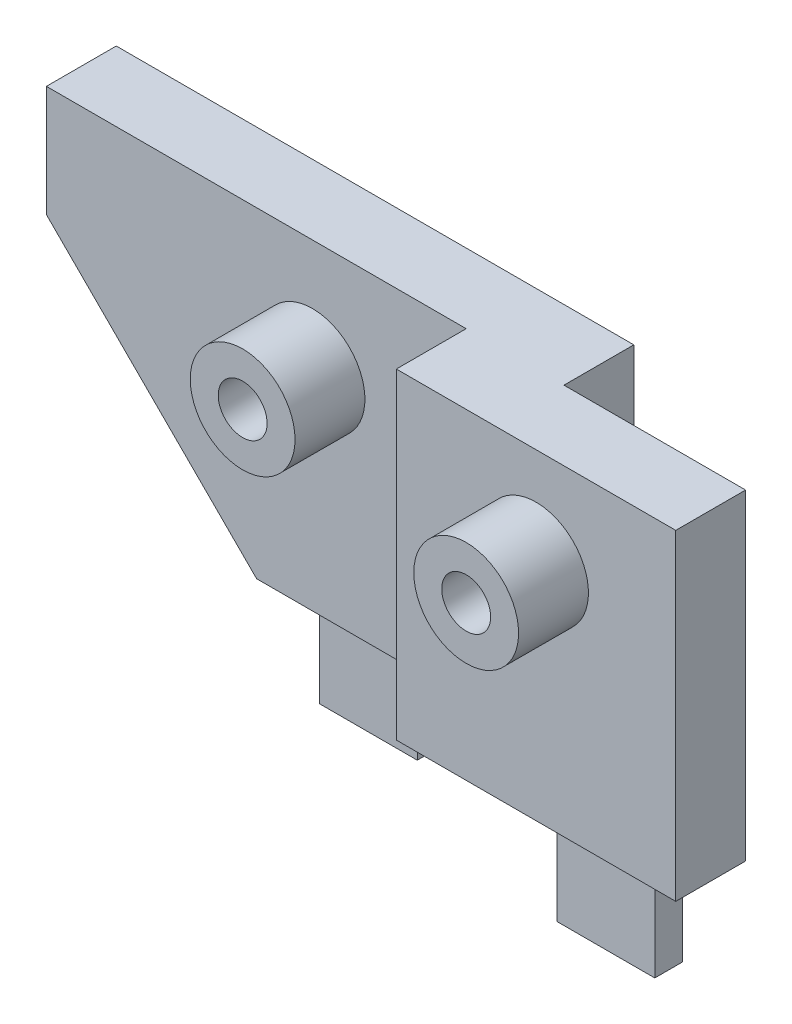
SolidWorks part; units mm, degrees
ref_plane "Front Plane" through (0, 0, 0) normal (0, 0, 1) x (1, 0, 0)
ref_plane "Top Plane" through (0, 0, 0) normal (0, 1, 0) x (1, 0, 0)
ref_plane "Right Plane" through (0, 0, 0) normal (1, 0, 0) x (0, 0, -1)
sketch "Sketch1" plane through (0, 0, 0) normal (0, 1, 0) x (1, 0, 0)
  line L0 (18, 0) -> (22, 0)
  line L1 (0, 0) -> (18, 0)
  line L2 (0, 0) -> (0, -5)
  line L3 (0, -5) -> (15, -5)
  line L4 (18, 0) -> (18, -10) construction
  line L5 (22, -5) -> (35, -5)
  line L6 (15, -5) -> (15, -10)
  line L7 (15, -10) -> (35, -10)
  line L8 (35, -5) -> (35, -10)
  line L9 (22, 0) -> (22, -5)
  dimension "D1" = 5
  dimension "D2" = 18
  dimension "D3" = 5
  dimension "D4" = 20
  dimension "D5" = 15
  dimension "D6" = 5
  dimension "D7" = 7
extrude "Boss-Extrude1" add sketch "Sketch1" along normal blind 23
sketch "Sketch2" plane through (0, 0, 10) normal (0, 0, 1) x (1, 0, 0)
  line L0 (35, 16) -> (25, 16) construction
  line L1 (35, 23) -> (35, 0) construction
  line L2 (15, 0) -> (35, 0) construction
  line L3 (0, 23) -> (0, 0) construction
  line L4 (0, 0) -> (15, 0) construction
  circle A0 centre (4, 15) radius 1.75
  circle A1 centre (25, 16) radius 1.75
  dimension "D5" = 3.5
  dimension "D6" = 3.5
  dimension "D1" = 10
  dimension "D2" = 16
  dimension "D3" = 4
  dimension "D4" = 15
extrude "Cut-Extrude1" cut sketch "Sketch2" against normal blind 10
sketch "Sketch3" plane through (0, 0, 0) normal (0, -1, 0) x (1, 0, 0)
  line L0 (15, 5) -> (22, 5) construction
  line L1 (18.5, 0) -> (18.5, 10) construction
  line L2 (22, 0) -> (0, 0) construction
  line L3 (15, 10) -> (35, 10) construction
  circle A0 centre (18.5, 5) radius 1.5
  point P10 (18.5, 5)
  dimension "D1" = 3
extrude "Cut-Extrude2" cut sketch "Sketch3" against normal blind 10 contours A0
sketch "Sketch4" plane through (0, 0, 0) normal (0, -1, 0) x (1, 0, 0)
  line L0 (0, 2.5) -> (22, 2.5) construction
  line L1 (0, 0) -> (0, 5) construction
  line L2 (22, 5) -> (22, 0) construction
  line L3 (15, 7.5) -> (35, 7.5) construction
  line L4 (15, 5) -> (15, 10) construction
  line L5 (35, 10) -> (35, 5) construction
  line L6 (22, 0) -> (0, 0) construction
  line L7 (10, 1.5) -> (3, 1.5)
  line L8 (10, 1.5) -> (10, 3.5)
  line L9 (10, 3.5) -> (3, 3.5)
  line L10 (3, 1.5) -> (3, 3.5)
  line L11 (10, 1.5) -> (3, 3.5) construction
  line L12 (10, 3.5) -> (3, 1.5) construction
  line L13 (32, 6.5) -> (25, 6.5)
  line L14 (32, 6.5) -> (32, 8.5)
  line L15 (32, 8.5) -> (25, 8.5)
  line L16 (25, 6.5) -> (25, 8.5)
  line L17 (32, 6.5) -> (25, 8.5) construction
  line L18 (32, 8.5) -> (25, 6.5) construction
  circle A0 centre (18.5, 5) radius 1.5 construction
  point P12 (6.5, 2.5)
  point P17 (28.5, 7.5)
  dimension "D8" = 18.5
  dimension "D7" = 3
  dimension "D1" = 2
  dimension "D2" = 7
  dimension "D3" = 3
  dimension "D4" = 2
  dimension "D5" = 7
  dimension "D6" = 3
  dimension "D9" = 5
extrude "Boss-Extrude2" add sketch "Sketch4" along normal blind 7
sketch "Sketch6" plane through (0, 0, 5) normal (0, 0, 1) x (1, 0, 0)
  circle A0 centre (4, 15) radius 1.75
  circle A1 centre (4, 15) radius 3.75
  dimension "D1" = 2
  dimension "D2" = 3.5
extrude "Boss-Extrude3" add sketch "Sketch6" along normal blind 5
sketch "Sketch7" plane through (0, 0, 10) normal (0, 0, 1) x (1, 0, 0)
  circle A0 centre (25, 16) radius 1.75
  circle A1 centre (25, 16) radius 3.75
  dimension "D1" = 3.5
  dimension "D2" = 2
extrude "Boss-Extrude4" add sketch "Sketch7" along normal blind 5 contours A1 | A0
sketch "Sketch10" plane through (0, 0, 5) normal (0, 0, 1) x (1, 0, 0)
  line L0 (0, 23) -> (-15.0472, 23)
  line L1 (-15.0472, 15.0472) -> (0, 0)
  line L2 (0, 23) -> (0, 0) construction
  line L3 (-15.0472, 23) -> (-15.0472, 15.0472)
  line L4 (0, 23) -> (0, 0)
  dimension "D1" = 45
  dimension "D2" = 21.28
extrude "Boss-Extrude5" add sketch "Sketch10" against normal blind 5
